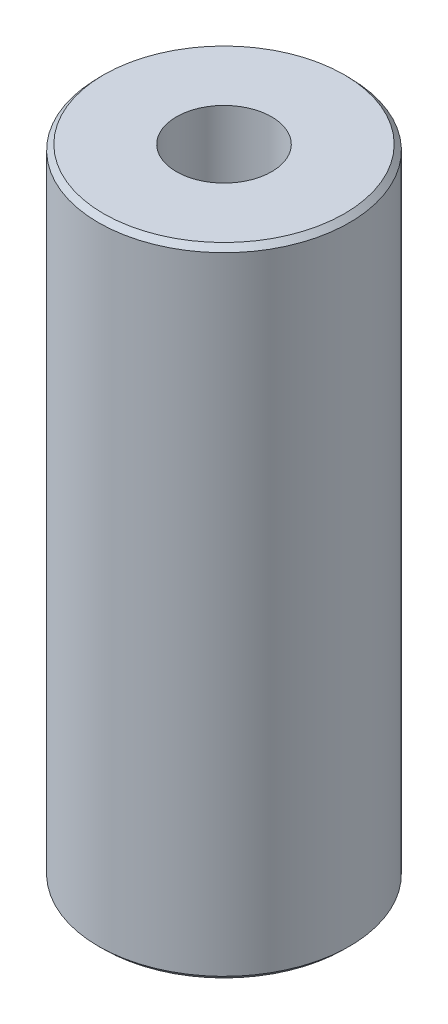
SolidWorks part; units mm, degrees
ref_plane "Front Plane" through (0, 0, 0) normal (0, 0, 1) x (1, 0, 0)
ref_plane "Top Plane" through (0, 0, 0) normal (0, 1, 0) x (1, 0, 0)
ref_plane "Right Plane" through (0, 0, 0) normal (1, 0, 0) x (0, 0, -1)
sketch "Sketch1" plane through (0, 0, 0) normal (0, 1, 0) x (1, 0, 0)
  circle A0 centre (0, 0) radius 10
  dimension "SHAFT_OD" = 20
extrude "Boss-Extrude1" add sketch "Sketch1" along normal blind 50.778
sketch "Sketch2" plane through (0, 0, 0) normal (0, 1, 0) x (1, 0, 0)
  circle A0 centre (0, 0) radius 3.7951
  dimension "BORE_D" = 7.5903
extrude "Cut-Extrude1" cut sketch "Sketch2" along normal through all
chamfer "Chamfer1" distance 0.416 angle 44.36 2 edges at (0, 50.778, 10) (0, 0, 10) first distance on face at (0, 50.778, 10) first distance on face at (0, 0, 3.7951)
